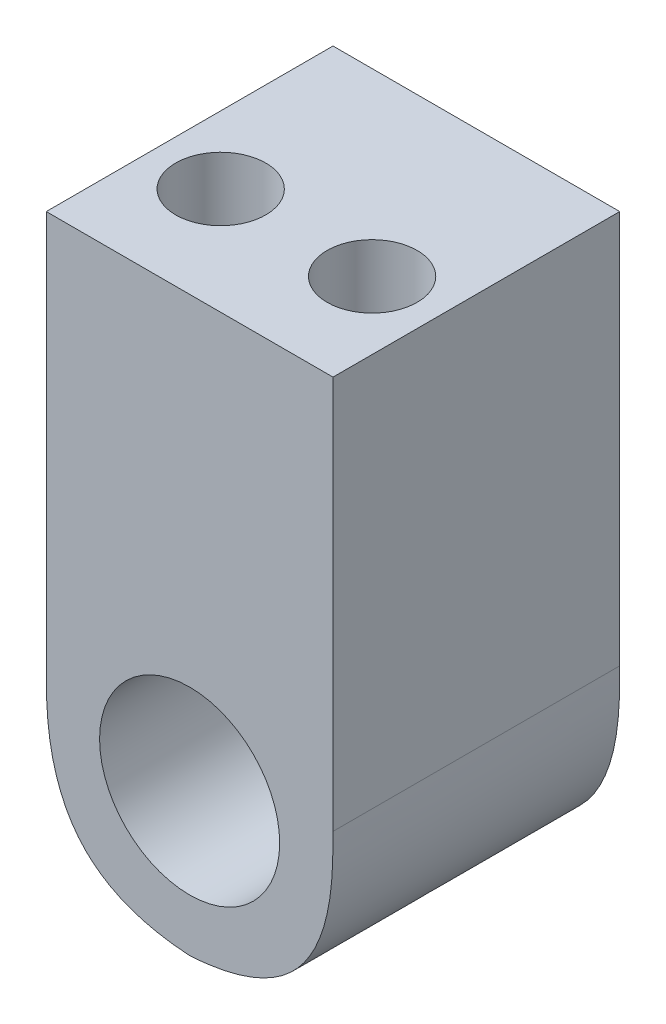
SolidWorks part; units mm, degrees
ref_plane "Front Plane" through (0, 0, 0) normal (0, 0, 1) x (1, 0, 0)
ref_plane "Top Plane" through (0, 0, 0) normal (0, 1, 0) x (1, 0, 0)
ref_plane "Right Plane" through (0, 0, 0) normal (1, 0, 0) x (0, 0, -1)
sketch "Sketch1" plane through (0, 0, 0) normal (0, 0, 1) x (1, 0, 0)
  line L1 (-6.35, 6.35) -> (6.35, 6.35)
  line L2 (-6.35, 6.35) -> (-6.35, -6.35)
  line L3 (-6.35, -6.35) -> (6.35, -6.35)
  line L4 (6.35, 6.35) -> (6.35, -6.35)
  line L5 (-6.35, 6.35) -> (6.35, -6.35) construction
  line L6 (-6.35, -6.35) -> (6.35, 6.35) construction
  line L7 (-6.35, 6.35) -> (6.35, 6.35)
  line L8 (-6.35, 6.35) -> (-6.35, 19.05)
  line L9 (-6.35, 19.05) -> (6.35, 19.05)
  line L10 (6.35, 6.35) -> (6.35, 19.05)
  circle A0 centre (0, 0) radius 3.9878
  point P0 (0, 0)
  dimension "D2" = 7.9756
  dimension "D1" = 12.7
  dimension "D3" = 12.7
  dimension "D4" = 12.7
extrude "Boss-Extrude1" add sketch "Sketch1" against normal blind 12.7 contours L1 L10 L9 L8 | L4 L1 L2 L3 A0 | A0 region at (0, 12.7, 0) region at (0, 6.1704, 0) region at (0, 0, 0)
fillet "Fillet1" radius 7.9756 2 edges at (-6.35, -6.35, -6.35) (6.35, -6.35, -6.35) curvature continuous yes
sketch "Sketch3" plane through (0, 19.05, 0) normal (0, 1, 0) x (1, 0, 0)
  line L0 (0, 4.7295) -> (-3.3528, 4.7295) construction
  line L1 (0, 4.7295) -> (3.3528, 4.7295) construction
  line L4 (-6.35, 0) -> (6.35, 0)
  line L5 (6.35, 0) -> (6.35, 12.7)
  line L6 (6.35, 12.7) -> (-6.35, 12.7)
  line L7 (-6.35, 12.7) -> (-6.35, 0)
  line L8 (-6.35, 0) -> (6.35, 0)
  line L9 (6.35, 0) -> (6.35, 12.7)
  line L10 (6.35, 12.7) -> (-6.35, 12.7)
  line L11 (-6.35, 12.7) -> (-6.35, 0)
  circle A0 centre (3.3528, 4.7295) radius 1.9939
  circle A1 centre (-3.3528, 4.7295) radius 1.9939
  point P2 (0, 0)
  point P4 (0, 0)
  dimension "D3" = 3.9878
  dimension "D4" = 3.9878
  dimension "D2" = 6.7056
  dimension "D5" = 4.7295
  dimension "D1" = 0
extrude "Cut-Extrude2" cut sketch "Sketch3" against normal blind 6.35 contours A0 | A0 | A0 | A0 | A1 | A1 | A1 | A1 region at (3.3528, 19.05, -4.7295) region at (-3.3528, 19.05, -4.7295)
extrude "Cut-Extrude3" cut sketch "Sketch1<3>" against normal through all contours A0
sketch "Sketch1<3>" plane through (0, 0, 0) normal (0, 0, 1) x (1, 0, 0) same geometry as "Sketch1"
